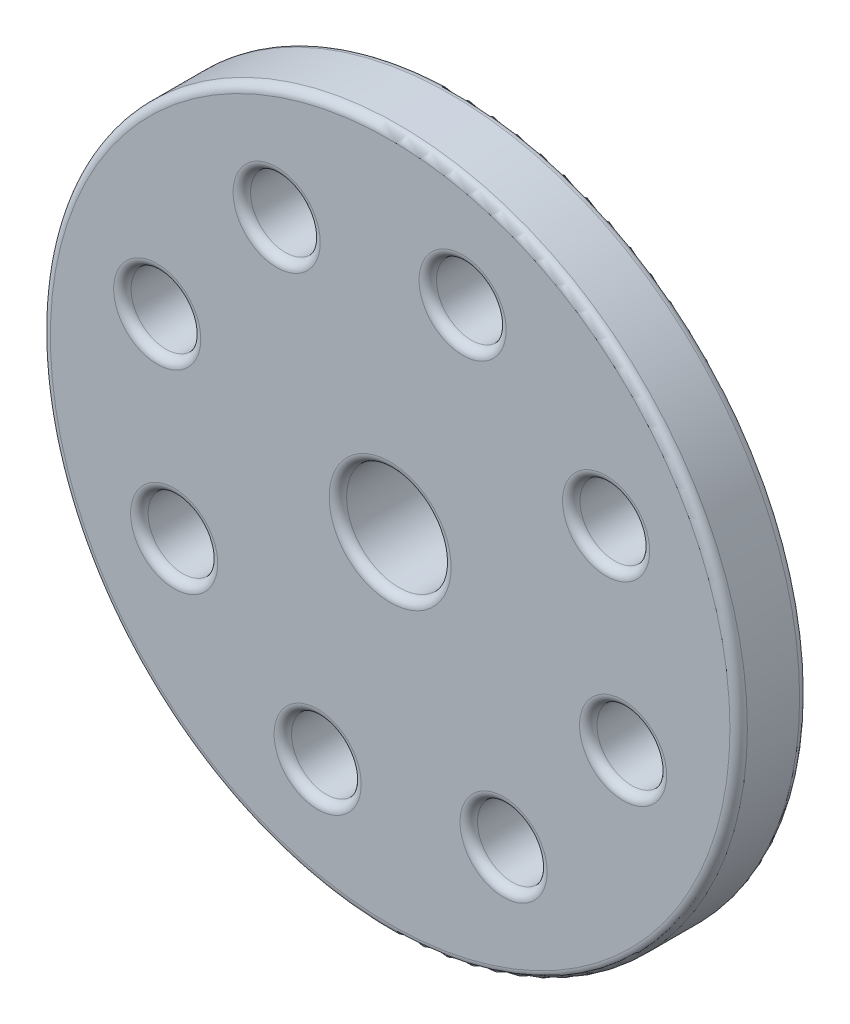
SolidWorks part; units mm, degrees
ref_plane "Plan de face" through (0, 0, 0) normal (0, 0, 1) x (1, 0, 0)
ref_plane "Plan de dessus" through (0, 0, 0) normal (0, 1, 0) x (1, 0, 0)
ref_plane "Plan de droite" through (0, 0, 0) normal (1, 0, 0) x (0, 0, -1)
sketch "Esquisse1" plane through (0, 0, 0) normal (0, 0, 1) x (1, 0, 0)
  line L0 (-17.7566, 4.338) -> (-14.5013, -1.859) construction
  line L1 (-16.5814, -8.5428) -> (-14.5013, -1.859) construction
  line L2 (-20.6983, -5.1143) -> (-14.5013, -1.859) construction
  line L3 (-21.1851, 0.2211) -> (-14.5013, -1.859) construction
  line L4 (-14.5013, -1.859) -> (-8.3043, 1.3963) construction
  line L5 (-11.246, -8.056) -> (-14.5013, -1.859) construction
  line L6 (-14.5013, -1.859) -> (-7.8175, -3.9391) construction
  line L7 (-12.4212, 4.8248) -> (-14.5013, -1.859) construction
  circle A0 centre (-14.5013, -1.859) radius 10
  circle A1 centre (-14.5013, -1.859) radius 1.5
  circle A2 centre (-16.5814, -8.5428) radius 1
  circle A3 centre (-21.1851, 0.2211) radius 1
  circle A4 centre (-12.4212, 4.8248) radius 1
  circle A5 centre (-7.8175, -3.9391) radius 1
  circle A6 centre (-11.246, -8.056) radius 1
  circle A7 centre (-17.7566, 4.338) radius 1
  circle A8 centre (-8.3043, 1.3963) radius 1
  circle A9 centre (-20.6983, -5.1143) radius 1
  dimension "D1" = 20
  dimension "D2" = 3
  dimension "D3" = 2
  dimension "D4" = 2
  dimension "D5" = 2
  dimension "D6" = 2
  dimension "D7" = 2
  dimension "D8" = 2
  dimension "D9" = 2
  dimension "D10" = 2
  dimension "D11" = 45
  dimension "D12" = 45
  dimension "D13" = 45
  dimension "D14" = 45
  dimension "D15" = 45
  dimension "D16" = 45
  dimension "D17" = 45
  dimension "D18" = 7
  dimension "D19" = 7
  dimension "D20" = 7
  dimension "D21" = 7
  dimension "D22" = 7
  dimension "D23" = 7
  dimension "D24" = 7
  dimension "D25" = 7
extrude "Boss.-Extru.1" add sketch "Esquisse1" along normal blind 2
sketch "Esquisse2" plane through (0, 0, 0) normal (0, 0, -1) x (-1, 0, 0)
  circle A0 centre (14.5013, -1.859) radius 5
  circle A1 centre (14.5013, -1.859) radius 1.5 construction
  circle A2 centre (14.5013, -1.859) radius 1.5
  dimension "D1" = 10
extrude "Boss.-Extru.2" add sketch "Esquisse2" along normal blind 1
fillet "Congé1" radius 1 1 edges at (-19.5013, -1.859, -1)
fillet "Congé2" radius 0.25 1 edges at (-4.5013, -1.859, 0)
fillet "Congé3" radius 0.25 1 edges at (-4.5013, -1.859, 2)
fillet "Congé4" radius 0.25 18 edges at (-16.0013, -1.859, -1) (-13.0013, -1.859, 2) (-6.8175, -3.9391, 0) (-6.8175, -3.9391, 2) (-10.246, -8.056, 0) (-10.246, -8.056, 2) (-15.5814, -8.5428, 0) (-15.5814, -8.5428, 2) (-19.6983, -5.1143, 0) (-19.6983, -5.1143, 2) (-20.1851, 0.2211, 0) (-20.1851, 0.2211, 2) (-16.7566, 4.338, 0) (-16.7566, 4.338, 2) (-11.4212, 4.8248, 0) (-11.4212, 4.8248, 2) (-7.3043, 1.3963, 0) (-7.3043, 1.3963, 2)
